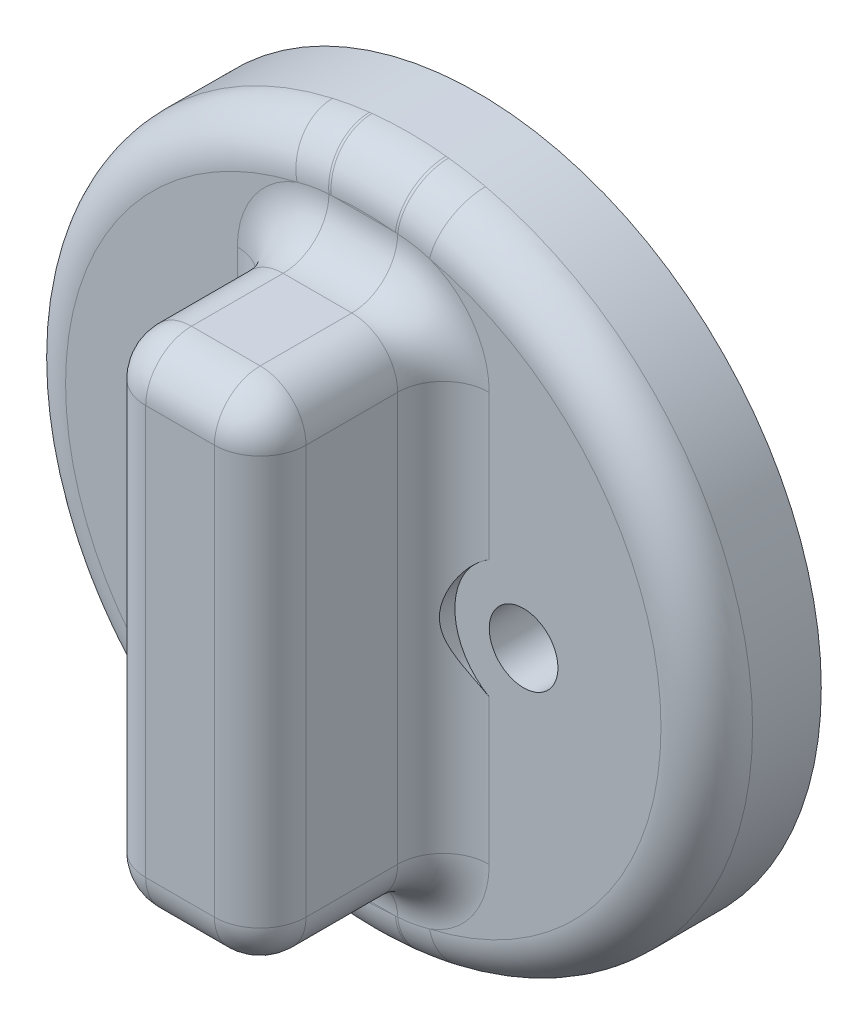
SolidWorks part; units mm, degrees
material "6061 Alloy"
ref_plane "Front Plane" through (0, 0, 0) normal (0, 0, 1) x (1, 0, 0)
ref_plane "Top Plane" through (0, 0, 0) normal (0, 1, 0) x (1, 0, 0)
ref_plane "Right Plane" through (0, 0, 0) normal (1, 0, 0) x (0, 0, -1)
sketch "Sketch2" plane through (0, 0, 0) normal (0, 0, 1) x (1, 0, 0)
  circle A0 centre (0, 0) radius 15
  point P3 (0, 0)
  dimension "D1" = 30
extrude "Boss-Extrude2" add sketch "Sketch2" along normal blind 5
sketch "Sketch3" plane through (0, 0, 5) normal (0, 0, 1) x (1, 0, 0)
  line L1 (-3.5, 10.9245) -> (3.5, 10.9245)
  line L2 (-3.5, 10.9245) -> (-3.5, -10.9245)
  line L3 (-3.5, -10.9245) -> (3.5, -10.9245)
  line L4 (3.5, 10.9245) -> (3.5, -10.9245)
  line L5 (0, -10.9245) -> (0, 10.9245) construction
  line L6 (-3.5, 0) -> (3.5, 0) construction
  point P0 (0, 0)
  dimension "D1" = 7
extrude "Boss-Extrude4" add sketch "Sketch3" along normal blind 8
fillet "Fillet1" radius 2 12 edges at (3.5, 0, 5) (3.5, 10.9245, 9) (0, 10.9245, 5) (-3.5, 10.9245, 9) (-3.5, 0, 5) (-3.5, -10.9245, 9) (3.5, -10.9245, 9) (0, -10.9245, 5) (0, -10.9245, 13) (-3.5, 0, 13) (0, 10.9245, 13) (3.5, 0, 13)
fillet "Fillet2" radius 2 1 edges at (15, 0, 5)
sketch "Sketch4" plane through (0, 0, 0) normal (0, 0, 1) x (1, 0, 0)
  line L0 (-7, 0) -> (0, 0) construction
  line L1 (0, 0) -> (0, -4.7782) construction
  circle A0 centre (-7, 0) radius 1.5
  circle A1 centre (7, 0) radius 1.5
  dimension "D1" = 3
  dimension "D2" = 7
extrude "M4_DRILL" cut sketch "Sketch4" along normal up to surface (5 mm away) up to face at (7.0172, 0, 5)
sketch "Sketch5" plane through (0, 0, 5) normal (0, 0, 1) x (1, 0, 0)
  circle A0 centre (-7, 0) radius 3
  circle A1 centre (7, 0) radius 3
  dimension "D1" = 6
  dimension "D2" = 6
extrude "Cut-Extrude1" cut sketch "Sketch5" along normal up to surface (8 mm away) up to face at (0, 0, 13)
